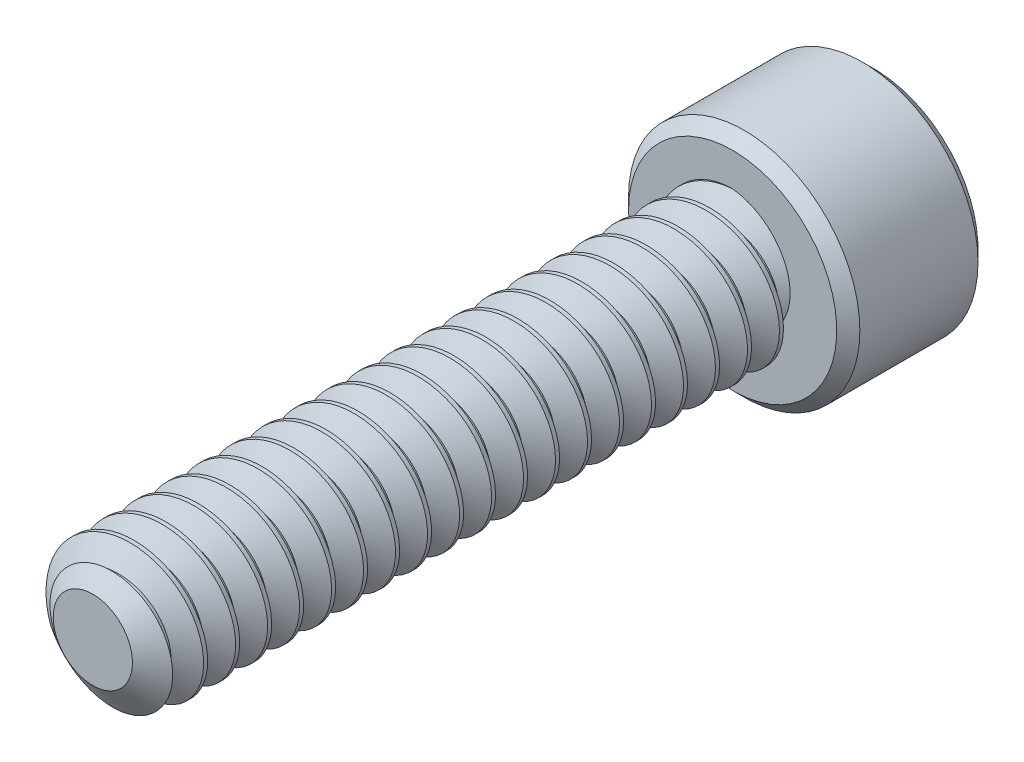
SolidWorks part; units mm, degrees
other "DetailItem1"
ref_plane "Front Plane" through (0, 0, 0) normal (0, 0, 1) x (1, 0, 0)
ref_plane "Top Plane" through (0, 0, 0) normal (0, 1, 0) x (1, 0, 0)
ref_plane "Right Plane" through (0, 0, 0) normal (1, 0, 0) x (0, 0, -1)
sketch "Sketch1" plane through (0, 0, 0) normal (0, 0, 1) x (1, 0, 0)
  circle A0 centre (0, 0) radius 1.7526
  dimension "OD" = 3.5052
extrude "Extrude1" add sketch "Sketch1" against normal blind 15.875
sketch "Sketch2" plane through (0, 0, 0) normal (0, 0, 1) x (1, 0, 0)
  circle A0 centre (0, 0) radius 1.7526 construction
  circle A1 centre (0, 0) radius 1.7526
curve "Helix/Spiral1" pitch 0.7937 height 16.6687 turns 21 parameters "pitch"=0.7937
sketch "Sketch3" plane through (0, 0, 0) normal (1, 0, 0) x (0, 0, -1)
  line L0 (-0.6945, 1.7526) -> (-0.3969, 1.237)
  line L1 (-0.3969, 1.237) -> (-0.2977, 1.237)
  line L2 (-0.2977, 1.237) -> (0, 1.7526)
  line L3 (-0.6945, 1.7526) -> (0, 1.7526)
  line L4 (-0.3473, 1.7526) -> (-0.3473, 1.237) construction
  line L5 (-0.5457, 1.4948) -> (-0.1488, 1.4948) construction
  line L6 (0, 1.7526) -> (0, -1.7526) construction
  dimension "D1" = 0.0992
  dimension "D2" = 0.3969
  dimension "D3" = 60
sweep "Cut-Sweep1" cut profiles "Sketch3" path "Helix/Spiral1"
sketch "Sketch4" plane through (0, 0, 0) normal (1, 0, 0) x (0, 0, -1)
  line L0 (0.5388, 1.7526) -> (0, 0.983)
  line L1 (0, 0.983) -> (0, 1.7526)
  line L2 (0.5388, 1.7526) -> (0, 1.7526)
  line L3 (-0.6945, 1.7526) -> (0, 1.7526) construction
  line L4 (0, 0) -> (7.0209, 0) construction
  dimension "D1" = 55
  dimension "D2" = 0.254
revolve "Cut-Revolve1" cut sketch "Sketch4" angle 360 about L4
sketch "Sketch5" plane through (0, 0, 0) normal (1, 0, 0) x (0, 0, -1)
  line L0 (15.875, -1.2539) -> (15.875, 1.2505) construction
  line L1 (15.875, 1.8796) -> (0.1202, 1.8796)
  line L2 (15.875, 1.8796) -> (15.875, 0)
  line L3 (15.875, 0) -> (0, 0)
  line L4 (0, 1.5494) -> (0, 0)
  line L5 (0.1202, 1.8796) -> (0, 1.5494)
  line L6 (0, 0) -> (9.9695, 0) construction
  point P3 (0, 1.8796)
  point P10 (0, 1.8796)
  dimension "D1" = 0.3302
  dimension "D2" = 0.127
  dimension "D3" = 20
  dimension "Min Thread" = 0
revolve "partially thread" [suppressed] add sketch "Sketch5" angle 360 about L6
sketch "Sketch6" plane through (0, 0, -15.875) normal (0, 0, -1) x (-1, 0, 0)
  circle A0 centre (0, 0) radius 2.8702
  dimension "head dia" = 5.7404
extrude "Extrude2" add sketch "Sketch6" along normal blind 3.5052
sketch "Sketch7" plane through (0, 0, -19.3802) normal (0, 0, -1) x (-1, 0, 0)
  line L1 (0, 1.604) -> (-1.3891, 0.802)
  line L2 (-1.3891, 0.802) -> (-1.3891, -0.802)
  line L3 (-1.3891, -0.802) -> (0, -1.604)
  line L4 (0, -1.604) -> (1.3891, -0.802)
  line L5 (1.3891, -0.802) -> (1.3891, 0.802)
  line L6 (1.3891, 0.802) -> (0, 1.604)
  circle A0 centre (0, 0) radius 1.3891 construction
  dimension "hex dia" = 2.7781
extrude "Cut-Extrude1" cut sketch "Sketch7" against normal blind 2.0836
sketch "Sketch8" plane through (0, 0, -19.3802) normal (0, 0, -1) x (-1, 0, 0)
  circle A0 centre (0, 0) radius 1.604
extrude "Cut-Extrude2" cut sketch "Sketch8" against normal through all draft 45
chamfer "Chamfer1" distance 0.287 angle 45 2 edges at (-2.8702, 0, -19.3802) (-2.8702, 0, -15.875)
sketch "Sketch9" plane through (0, 0, 0) normal (1, 0, 0) x (0, 0, -1)
  line L0 (0, 1.7526) -> (0, -1.7526) construction
  line L1 (1.9844, 1.7526) -> (1.9844, -1.7526) construction
  dimension "D1" = 1.9844
equation "\"D3@Helix/Spiral1\" = \"screw length@Extrude1\"+\"pitch@Helix/Spiral1\""
equation "\"D1@Sketch3\" = \"pitch@Helix/Spiral1\"*.125"
equation "\"D2@Sketch3\" = \"pitch@Helix/Spiral1\"*.5"
equation "\"D1@Cut-Extrude1\" = \"hex dia@Sketch7\"*.75"
equation "\"D1@Chamfer1\" = \"head dia@Sketch6\"*.05"
equation "\"D1@Sketch9\" = \"pitch@Helix/Spiral1\"*2.5"
